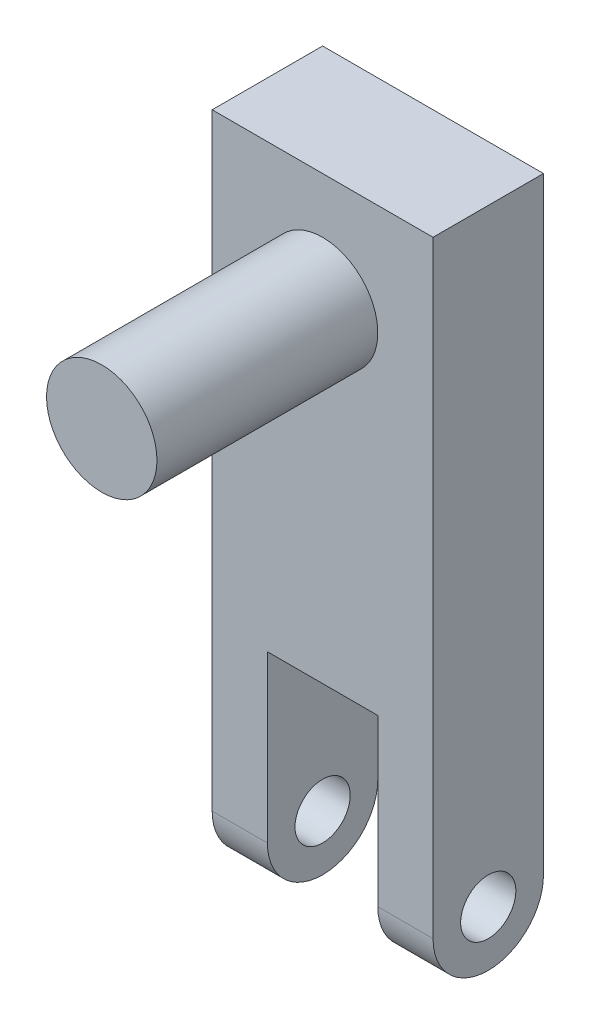
SolidWorks part; units mm, degrees
ref_plane "Front Plane" through (0, 0, 0) normal (0, 0, 1) x (1, 0, 0)
ref_plane "Top Plane" through (0, 0, 0) normal (0, 1, 0) x (1, 0, 0)
ref_plane "Right Plane" through (0, 0, 0) normal (1, 0, 0) x (0, 0, -1)
sketch "Sketch1" plane through (0, 0, 0) normal (0, 0, 1) x (1, 0, 0)
  line L0 (3.175, 0) -> (6.35, 0)
  line L1 (-6.35, 0) -> (-3.175, 0)
  line L2 (-6.35, 0) -> (-6.35, 38.1)
  line L3 (-6.35, 38.1) -> (6.35, 38.1)
  line L4 (6.35, 0) -> (6.35, 38.1)
  line L6 (-3.175, 0) -> (-3.175, 12.7)
  line L7 (-3.175, 12.7) -> (3.175, 12.7)
  line L8 (3.175, 0) -> (3.175, 12.7)
  point P4 (0, 12.7)
  point P5 (0, 38.1)
  dimension "D1" = 38.1
  dimension "D2" = 12.7
  dimension "D3" = 6.35
  dimension "D4" = 12.7
extrude "Boss-Extrude1" add sketch "Sketch1" along normal blind 6.35
fillet "Fillet1" radius 3.175 4 edges at (-4.7625, 0, 0) (-4.7625, 0, 6.35) (4.7625, 0, 0) (4.7625, 0, 6.35)
sketch "Sketch2" plane through (0, 0, 0) normal (1, 0, 0) x (0, 0, -1)
  circle A0 centre (-3.175, 3.175) radius 1.5875
  point P2 (0, 0)
  point P5 (0, 0)
  dimension "D1" = 3.175
extrude "Cut-Extrude1" cut sketch "Sketch2" against normal through all both and the other way through all
sketch "Sketch3" plane through (0, 0, 6.35) normal (0, 0, 1) x (1, 0, 0)
  line L0 (6.35, 38.1) -> (-6.35, 38.1) construction
  circle A0 centre (0, 31.75) radius 3.175
  dimension "D1" = 6.35
  dimension "D2" = 6.35
extrude "Boss-Extrude2" add sketch "Sketch3" along normal blind 12.7
